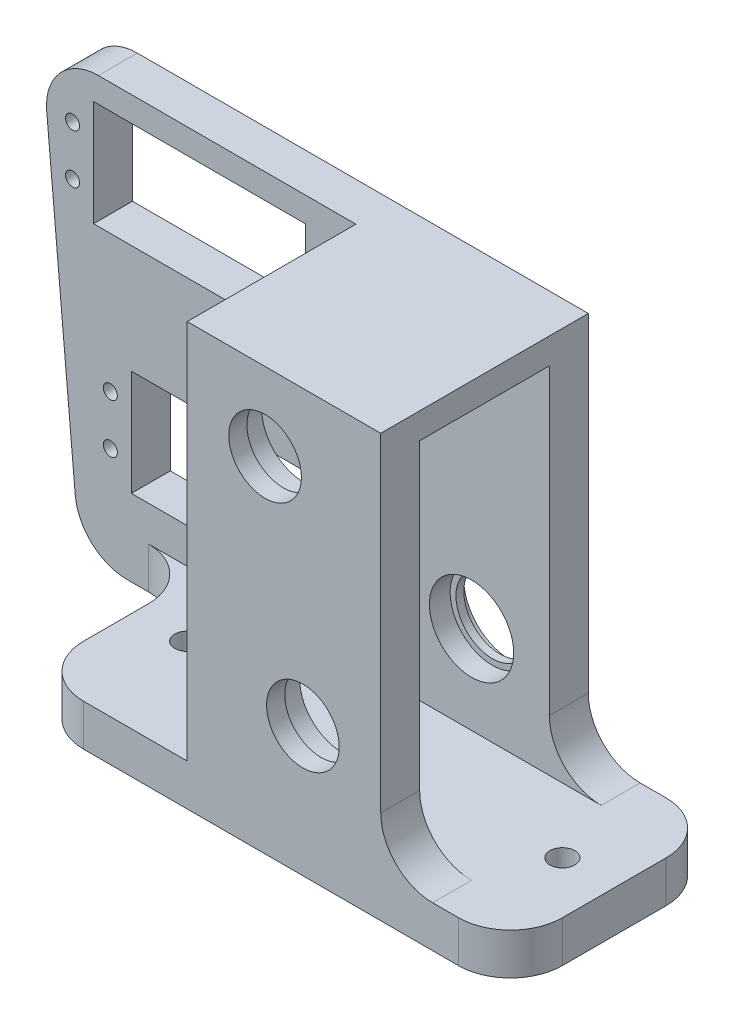
SolidWorks part; units mm, degrees
ref_plane "Front Plane" through (0, 0, 0) normal (0, 0, 1) x (1, 0, 0)
ref_plane "Top Plane" through (0, 0, 0) normal (0, 1, 0) x (1, 0, 0)
ref_plane "Right Plane" through (0, 0, 0) normal (1, 0, 0) x (0, 0, -1)
sketch "Sketch1" plane through (0, 0, 0) normal (0, 0, 1) x (1, 0, 0)
  line L0 (-52.2932, 0) -> (40, 0)
  line L1 (40, 0) -> (40, 8)
  line L2 (40, 8) -> (15, 8)
  line L3 (-52.2932, 0) -> (-52.2932, 8)
  line L4 (-52.2932, 8) -> (-22.2932, 8)
  line L5 (-22.2932, 81.3619) -> (15, 81.3619)
  line L6 (-22.2932, 8) -> (-22.2932, 81.3619)
  line L7 (15, 8) -> (15, 81.3619)
  line L8 (0, 25) -> (-7.2932, 66.3619) construction
  line L9 (0, 25) -> (0, 79.2) construction
  circle A1 centre (0, 25) radius 8.125
  circle A2 centre (-7.2932, 66.3619) radius 8.125
  point P0 (15, 10)
  point P4 (0, 0)
  dimension "D2" = 16.25
  dimension "D3" = 25
  dimension "D5" = 25
  dimension "D7" = 30
  dimension "D1" = 8
  dimension "D4" = 15
  dimension "D6" = 15
  dimension "D8" = 42
  dimension "D9" = 10
  dimension "D10" = 15
extrude "Boss-Extrude1" add sketch "Sketch1" along normal blind 40
sketch "Sketch2" plane through (0, 8, 0) normal (0, 1, 0) x (1, 0, 0)
  line L0 (-22.2932, -40) -> (-22.2932, 0) construction
  line L1 (-22.2932, -7.5) -> (15, -7.5)
  line L2 (-22.2932, -7.5) -> (-22.2932, -32.5)
  line L3 (-22.2932, -32.5) -> (15, -32.5)
  line L4 (15, -7.5) -> (15, -32.5)
  line L5 (15, -40) -> (15, 0) construction
  line L12 (40, -40) -> (40, 0) construction
  point P10 (40, -20)
  point P11 (15, -20)
  dimension "D1" = 25
extrude "Cut-Extrude1" cut sketch "Sketch2" along normal through all
hole_wizard "M4 Clearance Hole1" positions "Sketch8" profile "Sketch9" hole size "M4" standard "ANSI Metric" end condition through all
sketch "Sketch8" plane through (0, 8, 0) normal (0, 1, 0) x (1, 0, 0)
  line L0 (-22.2932, -7.5) -> (-22.2932, -32.5) construction
  line L2 (-52.2932, -40) -> (-52.2932, 0) construction
  line L3 (40, -40) -> (40, 0) construction
  point P0 (-42.2932, -20)
  point P2 (30, -20)
  point P12 (-22.2932, -20)
  dimension "D1" = 10
  dimension "D2" = 10
sketch "Sketch9" plane through (-42.2932, 8, 20) normal (1, 0, 0) x (0, 0, 1)
  line L0 (0, 0) -> (0, 8)
  line L1 (0, 8) -> (2.4, 8)
  line L2 (2.4, 8) -> (2.4, 0)
  line L5 (2.4, 0) -> (0, 0)
  line L11 (0, -6.35) -> (0, 107.95) construction
  dimension "Thru Hole Dia." = 4.8
  dimension "Thru Hole Depth" = 8
sketch "Sketch10" plane through (0, 0, 40) normal (0, 0, 1) x (1, 0, 0)
  circle A0 centre (-7.2932, 66.3619) radius 8.125
  circle A1 centre (0, 25) radius 10.837
  circle A2 centre (-7.2932, 66.3619) radius 7
  circle A3 centre (0, 25) radius 7
  circle A4 centre (-7.2932, 66.3619) radius 8.125 construction
  circle A5 centre (0, 25) radius 8.125 construction
  dimension "D2" = 14
  dimension "D4" = 14
extrude "Boss-Extrude2" add sketch "Sketch10" against normal offset from surface (3.5 mm away) 4 up to face at (-8.125, 25, 32.5)
sketch "Sketch11" plane through (0, 0, 0) normal (0, 0, -1) x (-1, 0, 0)
  circle A0 centre (7.2932, 66.3619) radius 8.125
  circle A1 centre (7.2932, 66.3619) radius 7
  circle A2 centre (0, 25) radius 8.125
  circle A3 centre (0, 25) radius 7
  circle A4 centre (0, 25) radius 8.125 construction
  circle A5 centre (7.2932, 66.3619) radius 8.125 construction
  dimension "D1" = 14
  dimension "D2" = 14
extrude "Boss-Extrude3" add sketch "Sketch11" against normal offset from surface (3.5 mm away) 4 up to face at (8.125, 25, 7.5)
ref_axis "Axis1" through (0, 25, 3.5) along (0, 0, -1)
ref_plane "Plane1" through (0, 25, 0) normal (0, -1, 0) x (-1, 0, 0)
ref_axis "Axis2" through (-7.2932, 66.3619, 3.5) along (0, 0, -1)
ref_plane "Plane2" through (0, 66.3619, 0) normal (0, -1, 0) x (-1, 0, 0)
sketch "Sketch12" plane through (0, 0, 0) normal (0, 0, -1) x (-1, 0, 0)
  line L0 (-22, 25) -> (22, 25) construction
  line L1 (22.2932, 0) -> (75.56, 0)
  line L2 (22.2932, 0) -> (22.2932, 81.3619)
  line L3 (22.2932, 81.3619) -> (82.8532, 81.3619)
  line L5 (-22, 66.3619) -> (22, 66.3619) construction
  line L6 (24.66, 35.2) -> (65.56, 35.2)
  line L7 (24.66, 35.2) -> (24.66, 14.8)
  line L8 (24.66, 14.8) -> (65.56, 14.8)
  line L9 (65.56, 35.2) -> (65.56, 14.8)
  line L10 (-15, 81.3619) -> (22.2932, 81.3619) construction
  line L11 (31.9532, 76.5619) -> (72.8532, 76.5619)
  line L12 (31.9532, 76.5619) -> (31.9532, 56.1619)
  line L13 (31.9532, 56.1619) -> (72.8532, 56.1619)
  line L14 (72.8532, 76.5619) -> (72.8532, 56.1619)
  line L15 (75.56, 0) -> (82.8532, 81.3619)
  line L16 (52.2932, 0) -> (-40, 0) construction
  line L17 (22.2932, 81.3619) -> (22.2932, 8) construction
  circle A0 centre (35, 25) radius 6.6 construction
  circle A1 centre (0, 25) radius 7 construction
  circle A2 centre (42.2932, 66.3619) radius 6.6 construction
  circle A3 centre (7.2932, 66.3619) radius 7 construction
  point P1 (0, 0)
  point P15 (45.11, 14.8)
  point P16 (65.56, 25)
  point P17 (80.816, 81.3619)
  point P18 (22.8024, 0)
  point P27 (31.9532, 66.3619)
  point P34 (52.4032, 56.1619)
  dimension "D7" = 13.2
  dimension "D11" = 13.2
  dimension "D2" = 20.4
  dimension "D3" = 40.9
  dimension "D4" = 10.11
  dimension "D9" = 10.11
  dimension "D5" = 35
  dimension "D6" = 10
  dimension "D8" = 10
extrude "Boss-Extrude4" add sketch "Sketch12" against normal up to surface (7.5 mm away) up to face at (8.125, 25, 7.5)
sketch "Sketch13" plane through (0, 0, 0) normal (0, 0, -1) x (-1, 0, 0)
  line L0 (24.66, 35.2) -> (24.66, 14.8) construction
  line L1 (-22, 25) -> (22, 25) construction
  line L2 (65.56, 14.8) -> (65.56, 35.2) construction
  line L3 (31.9532, 76.5619) -> (31.9532, 56.1619) construction
  line L5 (-22, 66.3619) -> (22, 66.3619) construction
  line L6 (72.8532, 56.1619) -> (72.8532, 76.5619) construction
  circle A0 centre (20.61, 29.75) radius 1.35
  circle A1 centre (20.61, 20.25) radius 1.35
  circle A2 centre (69.61, 29.75) radius 1.35
  circle A3 centre (69.61, 20.25) radius 1.35
  circle A4 centre (27.9032, 71.1119) radius 1.35
  circle A5 centre (27.9032, 61.6119) radius 1.35
  circle A6 centre (76.9032, 71.1119) radius 1.35
  circle A7 centre (76.9032, 61.6119) radius 1.35
  point P12 (0, 0)
  point P13 (0, 0)
  point P14 (0, 0)
  point P29 (0, 0)
  dimension "D1" = 2.7
  dimension "D6" = 2.7
  dimension "D2" = 4.05
  dimension "D3" = 9.5
  dimension "D4" = 4.75
  dimension "D5" = 4.05
  dimension "D7" = 9.5
  dimension "D8" = 4.05
  dimension "D9" = 4.75
  dimension "D10" = 4.05
extrude "Cut-Extrude2" cut sketch "Sketch13" against normal up to next
sketch "Sketch14" plane through (0, 0, 7.5) normal (0, 0, 1) x (1, 0, 0)
  line L0 (15, 8) -> (15, 81.3619) construction
  line L1 (15, 81.3619) -> (-22.2932, 81.3619)
  line L2 (15, 81.3619) -> (15, 76.3619)
  line L3 (15, 76.3619) -> (-22.2932, 76.3619)
  line L4 (-22.2932, 81.3619) -> (-22.2932, 76.3619)
  line L5 (15, 81.3619) -> (-22.2932, 81.3619) construction
  line L6 (-22.2932, 81.3619) -> (-22.2932, 8) construction
  dimension "D1" = 5
extrude "Boss-Extrude5" add sketch "Sketch14" along normal up to surface (25 mm away) up to face at (-8.125, 25, 32.5)
sketch "Sketch15" plane through (0, 0, 0) normal (0, 0, -1) x (-1, 0, 0)
  circle A0 centre (0, 25) radius 9
  circle A1 centre (7.2932, 66.3619) radius 9
  dimension "D1" = 18
extrude "Cut-Extrude3" cut sketch "Sketch15" against normal blind 2
fillet "Fillet1" radius 10 8 edges at (15, 8, 36.25) (15, 8, 3.75) (-82.8532, 81.3619, 3.75) (-75.56, 0, 3.75) (-52.2932, 4, 40) (40, 4, 40) (40, 4, 0) (-52.2932, 4, 7.5)
equation "\"D4@Sketch13\"=\"D3@Sketch13\"/2"
equation "\"D5@Sketch12\"=\"D1@Sketch12\""
equation "\"D8@Sketch13\"=\"D2@Sketch13\""
equation "\"D9@Sketch13\"=\"D7@Sketch13\"/2"
equation "\"D10@Sketch13\"=\"D5@Sketch13\""
